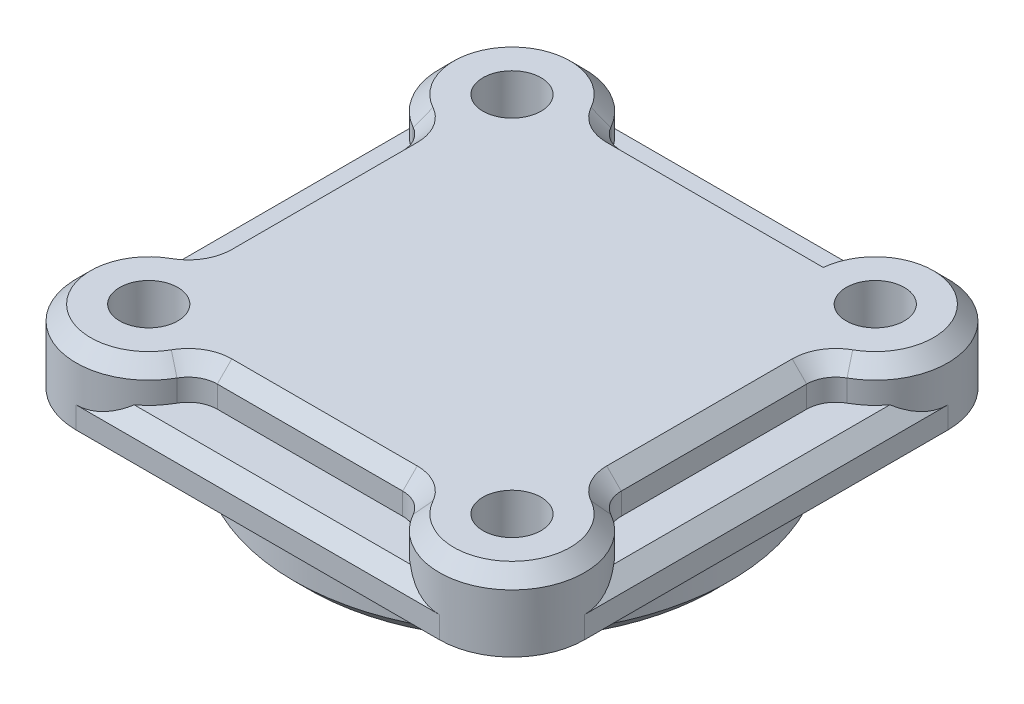
SolidWorks part; units mm, degrees
material "6061 Alloy"
ref_plane "Front Plane" through (0, 0, 0) normal (0, 0, 1) x (1, 0, 0)
ref_plane "Top Plane" through (0, 0, 0) normal (0, 1, 0) x (1, 0, 0)
ref_plane "Right Plane" through (0, 0, 0) normal (1, 0, 0) x (0, 0, -1)
sketch "Sketch1" plane through (0, 0, 0) normal (0, 1, 0) x (1, 0, 0)
  line L0 (-26.8003, 0) -> (39.2381, 0) construction
  line L1 (0, -23.9826) -> (0, 26.2978) construction
  line L3 (-15.875, -22.225) -> (15.875, -22.225)
  line L4 (-22.225, -15.875) -> (-22.225, 15.875)
  line L5 (-15.875, 22.225) -> (15.875, 22.225)
  line L6 (22.225, -15.875) -> (22.225, 15.875)
  arc A0 (-15.875, 22.225) -> (-22.225, 15.875) centre (-15.875, 15.875) ccw
  arc A1 (15.875, 22.225) -> (22.225, 15.875) centre (15.875, 15.875) cw
  arc A2 (-15.875, -22.225) -> (-22.225, -15.875) centre (-15.875, -15.875) cw
  arc A3 (15.875, -22.225) -> (22.225, -15.875) centre (15.875, -15.875) ccw
  point P5 (0, 0)
  point P6 (22.225, 0)
  point P7 (0, -22.225)
  dimension "D1" = 44.45
  dimension "D3" = 12.7
  dimension "D2" = 44.45
extrude "Boss-Extrude1" add sketch "Sketch1" along normal blind 3.175
sketch "Sketch2" plane through (0, 3.175, 0) normal (0, 1, 0) x (1, 0, 0)
  line L0 (0, -23.9826) -> (0, 26.2978) construction
  line L1 (-26.8003, 0) -> (39.2381, 0) construction
  line L2 (0, -23.9826) -> (0, 26.2978) construction
  line L3 (-26.8003, 0) -> (39.2381, 0) construction
  line L4 (-8.1045, 17.6536) -> (9.7792, 17.6536)
  line L5 (17.653, 8.1041) -> (17.653, -8.1041)
  line L6 (-8.1045, -17.6536) -> (8.1045, -17.6536)
  line L7 (-17.653, 8.1041) -> (-17.653, -8.1041)
  arc A0 (-15.875, 22.225) -> (-22.225, 15.875) centre (-15.875, 15.875) ccw construction
  arc A1 (-15.875, 22.225) -> (-22.225, 15.875) centre (-15.875, 15.875) ccw
  arc A2 (-10.3246, 18.9597) -> (-18.9593, 10.3244) centre (-15.875, 15.875) ccw
  arc A3 (9.7792, 17.6536) -> (18.9593, 10.3244) centre (15.875, 15.875) cw
  arc A4 (10.3246, -18.9597) -> (18.9593, -10.3244) centre (15.875, -15.875) ccw
  arc A5 (-10.3246, -18.9597) -> (-18.9593, -10.3244) centre (-15.875, -15.875) cw
  arc A6 (18.9593, 10.3244) -> (17.653, 8.1041) centre (20.193, 8.1041) ccw
  arc A7 (17.653, -8.1041) -> (18.9593, -10.3244) centre (20.193, -8.1041) ccw
  arc A8 (10.3246, -18.9597) -> (8.1045, -17.6536) centre (8.1045, -20.1936) ccw
  arc A9 (-8.1045, -17.6536) -> (-10.3246, -18.9597) centre (-8.1045, -20.1936) ccw
  arc A10 (-18.9593, -10.3244) -> (-17.653, -8.1041) centre (-20.193, -8.1041) ccw
  arc A11 (-17.653, 8.1041) -> (-18.9593, 10.3244) centre (-20.193, 8.1041) ccw
  arc A12 (-10.3246, 18.9597) -> (-8.1045, 17.6536) centre (-8.1045, 20.1936) ccw
  point P11 (17.653, 9.779)
  point P23 (17.653, -9.779)
  point P26 (9.7792, -17.6536)
  point P29 (-9.7792, -17.6536)
  point P32 (-17.653, -9.779)
  point P35 (-17.653, 9.779)
  point P38 (-9.7792, 17.6536)
  arc M3 (-15.875, 22.225) -> (-22.225, 15.875) centre (-15.875, 15.875) ccw
  arc M5 (-22.225, -15.875) -> (-15.875, -22.225) centre (-15.875, -15.875) ccw
  arc M7 (15.875, -22.225) -> (22.225, -15.875) centre (15.875, -15.875) ccw
  arc M9 (22.225, 15.875) -> (15.875, 22.225) centre (15.875, 15.875) ccw
  dimension "D3" = 2.54
  dimension "D1" = 17.6536
  dimension "D2" = 17.653
extrude "Boss-Extrude2" add sketch "Sketch2" along normal blind 3.175 contours A12 A2 A11 L7 A10 A5 A9 L6 A8 A4 A7 L5 A6 A3 L4 M3 M5 M7 M9 region at (-0.0028, 3.175, 0.0052)
sketch "Sketch3" plane through (0, 0, 0) normal (0, -1, 0) x (1, 0, 0)
  circle A0 centre (0, 0) radius 15.875
  circle A1 centre (0, 0) radius 19.05
  dimension "D1" = 31.75
  dimension "D2" = 38.1
extrude "Boss-Extrude3" add sketch "Sketch3" along normal blind 6.35
sketch "Sketch4" plane through (0, 6.35, 0) normal (0, 1, 0) x (1, 0, 0)
  line L0 (0, 0) -> (0, 23.4217) construction
  line L1 (0, 0) -> (24.4366, 0) construction
  circle A0 centre (-15.875, 15.875) radius 2.54
  arc A1 (-10.3246, 18.9597) -> (-18.9593, 10.3244) centre (-15.875, 15.875) ccw construction
  circle A2 centre (15.875, 15.875) radius 2.54
  circle A3 centre (-15.875, -15.875) radius 2.54
  circle A4 centre (15.875, -15.875) radius 2.54
  dimension "D1" = 5.08
extrude "Cut-Extrude1" cut sketch "Sketch4" against normal through all
chamfer "Chamfer1" distance 1.27 angle 45 21 edges at (0, -6.35, -15.875) (0, -6.35, -19.05) (19.8369, 6.35, -20.8374) (18.0038, 6.35, -9.3921) (17.653, 6.35, 0) (18.0038, 6.35, 9.3921) (20.3653, 6.35, 20.3649) (9.3924, 6.35, 18.0044) (0.8374, 6.35, -17.6536) (0, 6.35, 17.6536) (-9.3924, 6.35, -18.0044) (-9.3924, 6.35, 18.0044) (-20.3653, 6.35, -20.3649) (-20.3653, 6.35, 20.3649) (-18.0038, 6.35, -9.3921) (-18.0038, 6.35, 9.3921) (-17.653, 6.35, 0)
